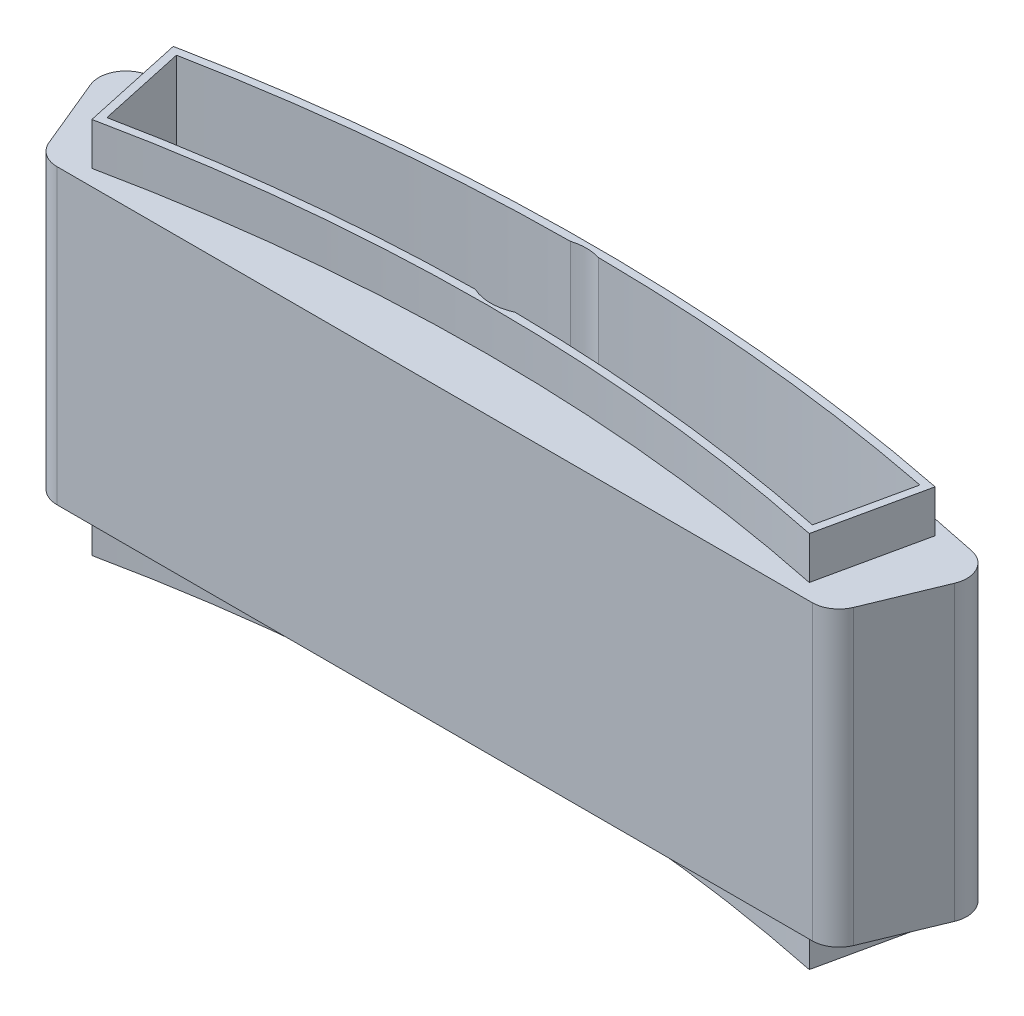
SolidWorks part; units mm, degrees
ref_plane "Front Plane" through (0, 0, 0) normal (0, 0, 1) x (1, 0, 0)
ref_plane "Top Plane" through (0, 0, 0) normal (0, 1, 0) x (1, 0, 0)
ref_plane "Right Plane" through (0, 0, 0) normal (1, 0, 0) x (0, 0, -1)
sketch "Sketch1" plane through (0, 0, 0) normal (0, 1, 0) x (1, 0, 0)
  line L0 (0, 35.0649) -> (0, -22.9896) construction
  line L1 (-34.3683, 0) -> (32.7428, 0) construction
  line L2 (-28.0194, 0.3027) -> (-26.106, -4.3167)
  line L3 (-24.5, -5.3996) -> (24.5, -5.3996)
  line L4 (-26.9097, 0.8898) -> (-24.9674, -3.7991)
  line L5 (26.8421, 0.7268) -> (24.9287, -3.8926)
  line L6 (28.0194, 0.3027) -> (26.0981, -4.3358)
  arc A0 (-26.106, -4.3167) -> (-24.5, -5.3996) centre (-24.4881, -3.6495) ccw
  arc A1 (26.0981, -4.3358) -> (24.5, -5.3996) centre (24.4881, -3.6494) cw
  arc A2 (24.3869, -4.1035) -> (-24.3869, -4.1035) centre (0, -116.488) ccw
  arc A3 (-24.9674, -3.7991) -> (-24.3869, -4.1035) centre (-24.4961, -3.6059) ccw
  arc A4 (-26.9097, 0.8898) -> (-26.5153, 1.5067) centre (-26.4143, 1.0077) cw
  arc A5 (-26.5153, 1.5067) -> (26.5153, 1.5067) centre (0, -120.6487) cw
  arc A6 (26.5153, 1.5067) -> (26.8421, 0.7268) centre (26.4239, 1.01) cw
  arc A7 (24.9287, -3.8926) -> (24.3869, -4.1035) centre (24.5039, -3.6027) cw
  arc A8 (26.774, 2.6854) -> (28.0194, 0.3027) centre (26.4035, 0.9749) cw
  arc A9 (-26.7737, 2.6827) -> (26.774, 2.6854) centre (0.0063, -120.6943) cw
  arc A10 (-28.0194, 0.3027) -> (-26.7737, 2.6827) centre (-26.4025, 0.9724) cw
  point P34 (0, -5.3996)
  point P35 (0, -1.488)
  point P36 (0, 4.3513)
  point P37 (0, 5.5557)
  dimension "D2" = 115
  dimension "D3" = 125
  dimension "D8" = 126.25
  dimension "D6" = 49
  dimension "D1" = 45
  dimension "D4" = 1.25
  dimension "D5" = 5
  dimension "D7" = 49
extrude "Boss-Extrude1" add sketch "Sketch1" along normal mid plane 19
sketch "Sketch5" plane through (0, 9.5, 0) normal (0, 1, 0) x (1, 0, 0)
  line L0 (-26.4143, 1.0077) -> (-24.4961, -3.6059) construction
  line L1 (26.4035, 0.9749) -> (24.5039, -3.6027) construction
  line L2 (-23.5381, 1.5922) -> (-22.5, -3.1891) construction
  line L3 (0, 0) -> (0, -8.4541) construction
  line L4 (23.5316, 1.5624) -> (22.5009, -3.1848) construction
  line L5 (-28.0194, 0.3027) -> (-26.106, -4.3167)
  line L6 (-24.5, -5.3996) -> (24.5, -5.3996)
  line L7 (26.0981, -4.3358) -> (28.0194, 0.3027)
  line L8 (-28.0194, 0.3027) -> (-26.106, -4.3167)
  line L9 (-24.5, -5.3996) -> (24.5, -5.3996)
  line L10 (26.0981, -4.3358) -> (28.0194, 0.3027)
  line L11 (23.5381, 1.5922) -> (23.5316, 1.5624) construction
  line L12 (22.5009, -3.1848) -> (22.5, -3.1891) construction
  line L13 (24.1287, 1.9556) -> (22.885, -3.7723)
  line L14 (-24.1353, 1.9861) -> (-22.8841, -3.7767)
  arc A0 (-23.5381, 1.5922) -> (23.5316, 1.5624) centre (-0.0812, -121.1871) cw construction
  arc A1 (22.5009, -3.1848) -> (-22.5, -3.1891) centre (0.0113, -115.9643) ccw construction
  arc A2 (-22.5, -3.1891) -> (-24.4961, -3.6059) centre (0.0113, -115.9643) ccw construction
  arc A3 (-26.4143, 1.0077) -> (-23.5381, 1.5922) centre (-0.0812, -121.1871) cw construction
  arc A4 (24.5039, -3.6027) -> (22.5009, -3.1848) centre (0.0113, -115.9643) ccw construction
  arc A5 (23.5316, 1.5624) -> (26.4035, 0.9749) centre (-0.0812, -121.1871) cw construction
  arc A6 (22.885, -3.7723) -> (-22.8841, -3.7767) centre (0.0113, -115.9643) ccw
  arc A7 (-26.7737, 2.6827) -> (-28.0194, 0.3027) centre (-26.4025, 0.9724) ccw
  arc A8 (-26.106, -4.3167) -> (-24.5, -5.3996) centre (-24.4881, -3.6495) ccw
  arc A9 (24.5, -5.3996) -> (26.0981, -4.3358) centre (24.4881, -3.6494) ccw
  arc A10 (28.0194, 0.3027) -> (26.774, 2.6854) centre (26.4035, 0.9749) ccw
  arc A11 (26.774, 2.6854) -> (-26.7737, 2.6827) centre (0.0063, -120.6943) ccw
  arc A12 (-26.7737, 2.6827) -> (-28.0194, 0.3027) centre (-26.4025, 0.9724) ccw
  arc A13 (-26.106, -4.3167) -> (-24.5, -5.3996) centre (-24.4881, -3.6495) ccw
  arc A14 (24.5, -5.3996) -> (26.0981, -4.3358) centre (24.4881, -3.6494) ccw
  arc A15 (28.0194, 0.3027) -> (26.774, 2.6854) centre (26.4035, 0.9749) ccw
  arc A16 (26.774, 2.6854) -> (-26.7737, 2.6827) centre (0.0063, -120.6943) ccw
  arc A17 (-24.1353, 1.9861) -> (24.1287, 1.9556) centre (-0.0812, -121.1871) cw
  dimension "D1" = 125
  dimension "D2" = 115
  dimension "D3" = 0
  dimension "D4" = 45
  dimension "D5" = 24.5
  dimension "D6" = 0.5
extrude "Boss-Extrude4" add sketch "Sketch5" against normal up to surface (19 mm away) up to face at (-0.0014, -9.5, 1.3131)
sketch "Sketch6" plane through (0, 9.5, 0) normal (0, 1, 0) x (1, 0, 0)
  line L0 (-23.5381, 1.5922) -> (-22.5, -3.1891)
  line L1 (22.5009, -3.1848) -> (23.5316, 1.5624)
  line L6 (-24.732, 2.378) -> (-23.2677, -4.3664)
  line L7 (23.2687, -4.3619) -> (24.7253, 2.3468)
  arc A0 (22.5009, -3.1848) -> (-22.5, -3.1891) centre (0.0113, -115.9643) ccw
  arc A1 (23.5316, 1.5624) -> (-23.5381, 1.5922) centre (-0.0812, -121.1871) ccw
  arc A6 (24.7253, 2.3468) -> (-24.732, 2.378) centre (-0.0812, -121.1871) ccw
  arc A7 (23.2687, -4.3619) -> (-23.2677, -4.3664) centre (0.0113, -115.9643) ccw
  dimension "D1" = 1
extrude "Boss-Extrude5" add sketch "Sketch6" along normal blind 2.75
mirror "Mirror1" about plane through (0, 0, 0) normal (0, 1, 0) of "Boss-Extrude5"
extrude "Cut-Extrude1" cut sketch "Sketch5<2>" against normal through all both and the other way through all contours A17 L13 A6 L14
sketch "Sketch5<2>" plane through (0, 9.5, 0) normal (0, 1, 0) x (1, 0, 0) same geometry as "Sketch5"
sketch "Sketch8" plane through (0, 12.2, 0) normal (0, 1, 0) x (1, 0, 0)
  circle A0 centre (0, 1.3457) radius 3.1
  dimension "D1" = 6.2
extrude "Cut-Extrude2" cut sketch "Sketch8" against normal through all both and the other way through all
